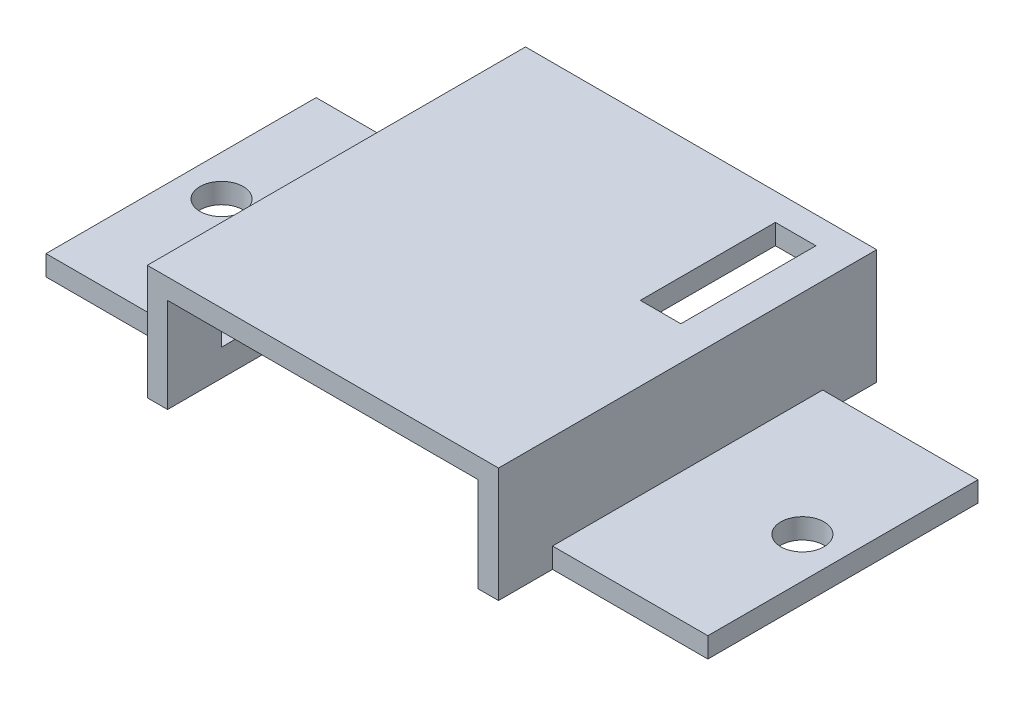
SolidWorks part; units mm, degrees
material "PEI"
ref_plane "Front Plane" through (0, 0, 0) normal (0, 0, 1) x (1, 0, 0)
ref_plane "Top Plane" through (0, 0, 0) normal (0, 1, 0) x (1, 0, 0)
ref_plane "Right Plane" through (0, 0, 0) normal (1, 0, 0) x (0, 0, -1)
sketch "Sketch1" plane through (0, 0, 0) normal (0, 0, 1) x (1, 0, 0)
  line L0 (0, 8.5) -> (0, -9.3416) construction
  line L1 (0, 0) -> (-24.5, 0)
  line L2 (-24.5, 0) -> (-24.5, 1.5)
  line L3 (-24.5, 1.5) -> (-13, 1.5)
  line L4 (-13, 1.5) -> (-13, 8.5)
  line L5 (-13, 8.5) -> (0, 8.5)
  line L6 (0, 8.5) -> (0, 7)
  line L7 (0, 7) -> (-11.5, 7)
  line L8 (-11.5, 7) -> (-11.5, 0)
  dimension "D1" = 1.5
  dimension "D2" = 1.5
  dimension "D3" = 11.5
  dimension "D4" = 24.5
  dimension "D5" = 1.5
  dimension "D6" = 7
extrude "Boss-Extrude1" add sketch "Sketch1" along normal mid plane 28 contours L8 L7 L6 L5 L4 L3 L2 L1 region at (-12.25, 4.25, 0)
mirror "Mirror1" about plane through (0, 0, 0) normal (1, 0, 0) of "Boss-Extrude1"
sketch "Sketch2" plane through (0, 8.5, 0) normal (0, 1, 0) x (1, 0, 0)
  line L0 (24.5, 14) -> (13, 14) construction
  line L1 (13, 14) -> (13, -14) construction
  line L2 (13, -14) -> (24.5, -14) construction
  line L3 (24.5, -14) -> (24.5, 14) construction
  line L4 (13, 14) -> (-13, 14)
  line L5 (-13, 14) -> (-13, -14)
  line L6 (-13, -14) -> (13, -14)
  line L7 (13, -14) -> (13, 14)
  line L8 (13, 14) -> (-13, 14)
  line L9 (-13, 14) -> (-13, -14)
  line L10 (-13, -14) -> (13, -14)
  line L11 (13, -14) -> (13, 14)
  line L12 (-13, 14) -> (-24.5, 14) construction
  line L13 (-24.5, 14) -> (-24.5, -14) construction
  line L14 (-24.5, -14) -> (-13, -14) construction
  line L15 (-13, -14) -> (-13, 14) construction
  line L16 (24.5, 14) -> (13, 14)
  line L17 (13, 14) -> (13, -14)
  line L18 (13, -14) -> (24.5, -14)
  line L19 (24.5, -14) -> (24.5, 14)
  line L20 (-13, 14) -> (-24.5, 14)
  line L21 (-24.5, 14) -> (-24.5, -14)
  line L22 (-24.5, -14) -> (-13, -14)
  line L23 (-13, -14) -> (-13, 14)
  line L24 (-13, 10) -> (-24.5, 10)
  line L25 (-13, -10) -> (-24.5, -10)
  line L26 (0, 0) -> (0, 14)
  line L27 (13, -10) -> (24.5, -10)
  line L28 (13, 10) -> (24.5, 10)
  line M10 (-13, 14) -> (-13, -14)
  line M12 (13, -14) -> (13, 14)
  dimension "D2" = 4
  dimension "D3" = 4
  dimension "D1" = 0
extrude "Cut-Extrude1" cut sketch "Sketch2" against normal through all contours L24 L20 L21 M10 | L25 L21 L22 M10 | L28 L19 L16 M12 | L27 L18 L19 M12 region at (18.75, 8.5, -12) region at (-18.75, 8.5, -12) region at (18.75, 8.5, 12) region at (-18.75, 8.5, 12)
sketch "Sketch4" plane through (0, 1.5, 0) normal (0, 1, 0) x (1, 0, 0)
  line L0 (24.5, 0) -> (21.5, 0)
  line L1 (0, 0) -> (0, -15.3594)
  line L4 (24.5, -10) -> (24.5, 10)
  line L5 (24.5, 10) -> (13, 10)
  line L6 (13, 10) -> (13, -10)
  line L7 (13, -10) -> (24.5, -10)
  line L8 (24.5, -10) -> (24.5, 10)
  line L9 (24.5, 10) -> (13, 10)
  line L10 (13, 10) -> (13, -10)
  line L11 (13, -10) -> (24.5, -10)
  circle A0 centre (21.5, 0) radius 1.6
  circle A1 centre (-21.5, 0) radius 1.6
  dimension "D3" = 3.2
  dimension "D2" = 3
  dimension "D1" = 0
extrude "Cut-Extrude2" cut sketch "Sketch4" against normal through all contours A0 | A1 region at (19.9453, 1.5, 0) region at (-21.5, 1.5, 0)
sketch "Sketch5" plane through (-11.5, 0, 0) normal (1, 0, 0) x (0, 0, -1)
  line L0 (-14, 0) -> (-10, 0)
  line L1 (-10, 0) -> (-10, 7)
  line L2 (-10, 7) -> (-2, 7)
  line L3 (-2, 7) -> (-2, 2)
  line L4 (14, 0) -> (14, 7)
  line L5 (14, 7) -> (-14, 7)
  line L6 (-14, 7) -> (-14, 0)
  line L7 (-14, 0) -> (14, 0)
  line L8 (14, 0) -> (14, 7)
  line L9 (14, 7) -> (-14, 7)
  line L10 (-14, 7) -> (-14, 0)
  line L11 (-14, 0) -> (14, 0)
  line L12 (-2, 2) -> (-10, 2)
  line M10 (14, 7) -> (-14, 7)
  dimension "D2" = 2
  dimension "D3" = 4
  dimension "D4" = 8
  dimension "D1" = 0
extrude "Cut-Extrude3" cut sketch "Sketch5" against normal through all contours L12 L3 L1 M10 region at (-11.5, 4.5, 6)
sketch "Sketch7" plane through (0, 8.5, 0) normal (0, 1, 0) x (1, 0, 0)
  line L1 (13, 14) -> (7.5, 14)
  line L2 (13, 14) -> (13, 2)
  line L3 (13, 2) -> (7.5, 2)
  line L4 (13, 14) -> (-13, 14)
  line L5 (-13, 14) -> (-13, -14)
  line L6 (-13, -14) -> (13, -14)
  line L7 (13, -14) -> (13, 14)
  line L8 (13, 14) -> (-13, 14)
  line L9 (-13, 14) -> (-13, -14)
  line L10 (-13, -14) -> (13, -14)
  line L11 (13, -14) -> (13, 14)
  line L12 (7.5, 14) -> (7.5, 2)
  line L13 (7.5, 2) -> (10.5, 2)
  line L14 (7.5, 2) -> (7.5, 12)
  line L15 (7.5, 12) -> (10.5, 12)
  line L16 (10.5, 2) -> (10.5, 12)
  dimension "D2" = 5.5
  dimension "D3" = 12
  dimension "D4" = 2
  dimension "D5" = 2.5
  dimension "D1" = 0
extrude "Cut-Extrude4" cut sketch "Sketch7" against normal up to surface (1.5 mm away) contours L3 L16 L15 L12 region at (9, 8.5, -7) up to face at (-6.125, 7, 3)
